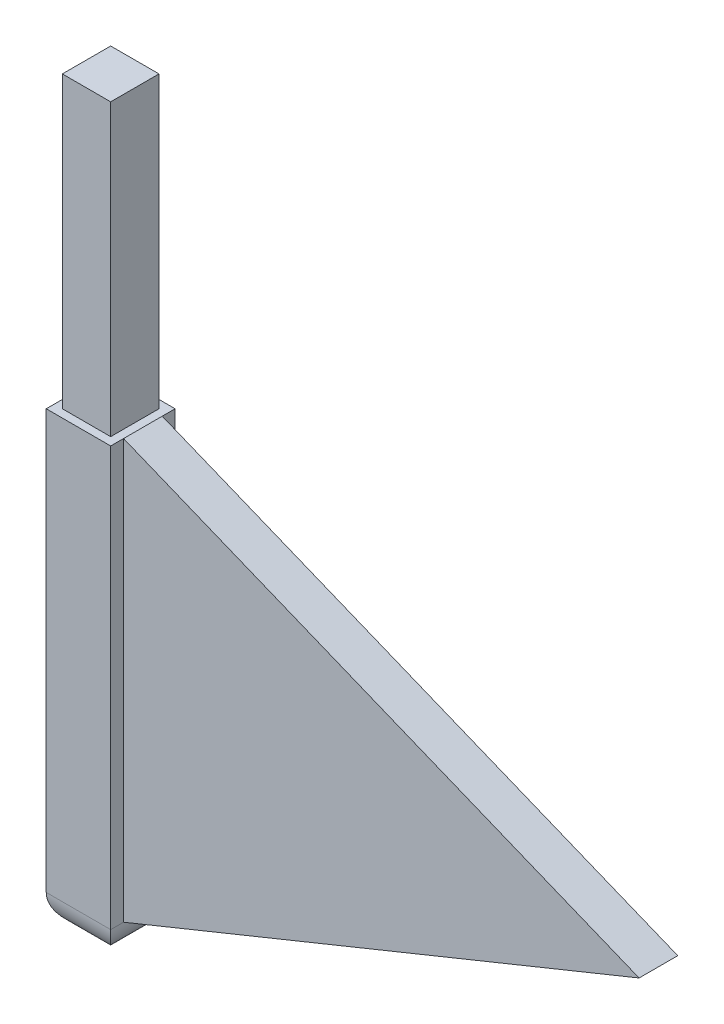
SolidWorks part; units mm, degrees
ref_plane "Front Plane" through (0, 0, 0) normal (0, 0, 1) x (1, 0, 0)
ref_plane "Top Plane" through (0, 0, 0) normal (0, 1, 0) x (1, 0, 0)
ref_plane "Right Plane" through (0, 0, 0) normal (1, 0, 0) x (0, 0, -1)
sketch "Sketch1" plane through (0, 0, 0) normal (0, 1, 0) x (1, 0, 0)
  line L1 (0, 0) -> (2.54, 0)
  line L2 (0, 0) -> (0, 2.54)
  line L3 (0, 2.54) -> (2.54, 2.54)
  line L4 (2.54, 0) -> (2.54, 2.54)
  dimension "D1" = 2.54
extrude "Boss-Extrude1" add sketch "Sketch1" along normal blind 29.21
sketch "Sketch2" plane through (0, 29.21, 0) normal (0, 1, 0) x (1, 0, 0)
  line L0 (2.54, 2.54) -> (0, 2.54) construction
  line L1 (0.3175, 0.3175) -> (2.2225, 0.3175)
  line L2 (0.3175, 0.3175) -> (0.3175, 2.2225)
  line L3 (0.3175, 2.2225) -> (2.2225, 2.2225)
  line L4 (2.2225, 0.3175) -> (2.2225, 2.2225)
  line L5 (2.54, 0) -> (2.54, 2.54) construction
  dimension "D1" = 1.905
  dimension "D2" = 0.3175
  dimension "D3" = 0.3175
extrude "Cut-Extrude1" cut sketch "Sketch2" against normal blind 11.43 flip side to cut
fillet "Fillet1" radius 1.27 4 edges at (0, 0, -1.27) (1.27, 0, -2.54) (2.54, 0, -1.27) (1.27, 0, 0)
sketch "Sketch3" plane through (2.54, 0, 0) normal (1, 0, 0) x (0, 0, -1)
  line L0 (0, 17.78) -> (2.54, 17.78) construction
  line L1 (0.508, 17.78) -> (2.032, 17.78)
  line L2 (0.508, 17.78) -> (0.508, 1.27)
  line L3 (0.508, 1.27) -> (2.032, 1.27)
  line L4 (2.032, 17.78) -> (2.032, 1.27)
  line L5 (0, 1.27) -> (2.54, 1.27) construction
  line L6 (2.54, 17.78) -> (2.54, 1.27) construction
  line L7 (0, 17.78) -> (0, 1.27) construction
  dimension "D1" = 0.508
  dimension "D2" = 0.508
extrude "Boss-Extrude2" add sketch "Sketch3" along normal blind 20.32
sketch "Sketch4" plane through (0, 0, -0.508) normal (0, 0, 1) x (1, 0, 0)
  line L0 (2.54, 17.78) -> (22.86, 9.525)
  line L1 (22.86, 17.78) -> (22.86, 1.27) construction
  line L4 (2.54, 17.78) -> (22.86, 17.78)
  line L5 (22.86, 17.78) -> (22.86, 9.525)
extrude "Cut-Extrude2" cut sketch "Sketch4" against normal through all
sketch "Sketch5" plane through (0, 0, -0.508) normal (0, 0, 1) x (1, 0, 0)
  line L0 (2.54, 1.27) -> (22.86, 9.525)
  line L1 (22.86, 9.525) -> (22.86, 1.27)
  line L2 (22.86, 1.27) -> (2.54, 1.27)
extrude "Cut-Extrude3" cut sketch "Sketch5" against normal through all
